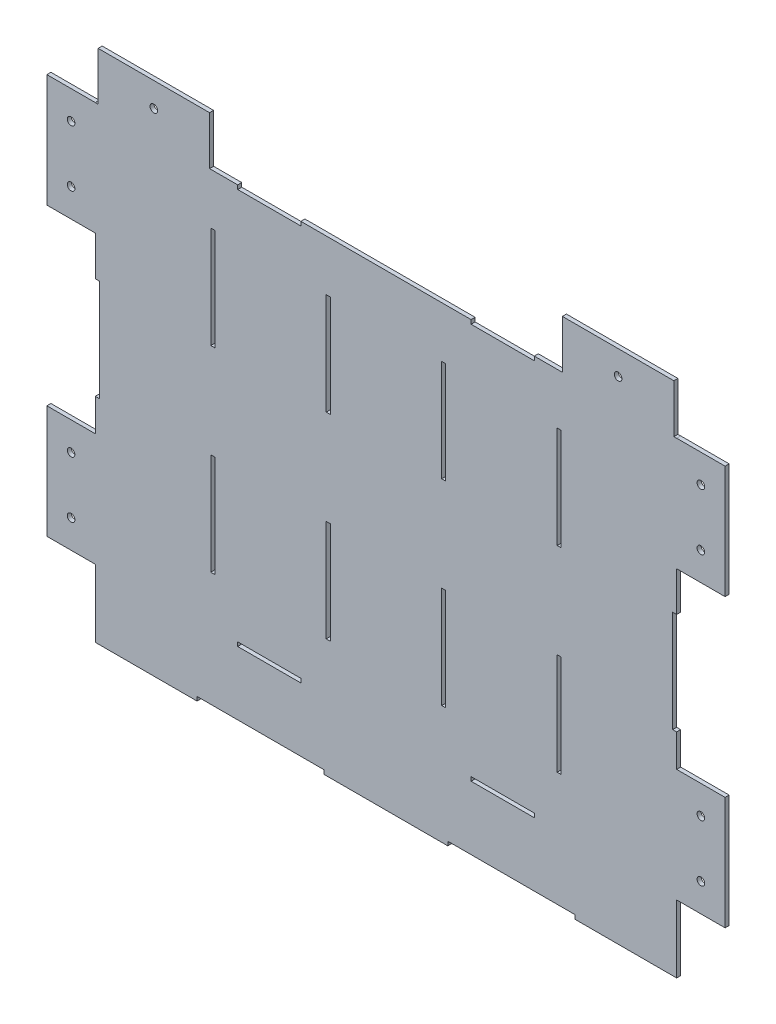
SolidWorks part; units mm, degrees
material "Custom Plastic"
ref_plane "X-Y Datum" through (0, 0, 0) normal (0, 0, 1) x (1, 0, 0)
ref_plane "X-Z Datum" through (0, 0, 0) normal (0, 1, 0) x (1, 0, 0)
ref_plane "Y-Z Datum" through (0, 0, 0) normal (1, 0, 0) x (0, 0, -1)
sketch "Sketch1" plane through (0, 0, 0) normal (0, 0, 1) x (1, 0, 0)
  line L0 (-228.6115, 0) -> (228.6115, 0) construction
  line L1 (-228.6115, -157.216) -> (228.6115, -157.216)
  line L2 (-228.6115, -157.216) -> (-228.6115, 157.216)
  line L3 (-228.6115, 157.216) -> (228.6115, 157.216)
  line L4 (228.6115, -157.216) -> (228.6115, 157.216)
  line L5 (-228.6115, -157.216) -> (228.6115, 157.216) construction
  line L6 (-228.6115, 157.216) -> (228.6115, -157.216) construction
  line L8 (-228.6115, 0) -> (-134.6215, 0) construction
  line L9 (-225.4325, -154.041) -> (-225.4325, 154.041)
  line L10 (-224.4165, -153.025) -> (-138.8165, -153.025) construction
  line L15 (-224.4165, -153.025) -> (-224.4165, 153.025) construction
  line L16 (-224.4165, 153.025) -> (-138.8165, 153.025) construction
  line L17 (-138.8165, -153.025) -> (-138.8165, 153.025) construction
  line L18 (-224.4165, -153.025) -> (-138.8165, 153.025) construction
  line L19 (-224.4165, 153.025) -> (-138.8165, -153.025) construction
  line L20 (-225.4325, 154.041) -> (-137.8005, 154.041)
  line L21 (-137.8005, -154.041) -> (-137.8005, 154.041)
  line L22 (-225.4325, -154.041) -> (-137.8005, -154.041)
  line L26 (-134.6255, 154.041) -> (-46.9935, 154.041)
  line L27 (-133.6095, -153.025) -> (-48.0095, -153.025) construction
  line L28 (-133.6095, -153.025) -> (-133.6095, 153.025) construction
  line L29 (-133.6095, 153.025) -> (-48.0095, 153.025) construction
  line L30 (-48.0095, -153.025) -> (-48.0095, 153.025) construction
  line L31 (-133.6095, -153.025) -> (-48.0095, 153.025) construction
  line L32 (-133.6095, 153.025) -> (-48.0095, -153.025) construction
  line L33 (-46.9935, -154.041) -> (-46.9935, 154.041)
  line L34 (-134.6255, -154.041) -> (-46.9935, -154.041)
  line L35 (-134.6255, -154.041) -> (-134.6255, 154.041)
  line L36 (42.7975, -153.025) -> (42.7975, 153.025) construction
  line L37 (43.8135, -154.041) -> (43.8135, 154.041)
  line L38 (-42.8025, -153.025) -> (42.7975, 153.025) construction
  line L39 (-42.8025, 153.025) -> (42.7975, -153.025) construction
  line L40 (-42.8025, -153.025) -> (-42.8025, 153.025) construction
  line L41 (-43.8185, -154.041) -> (-43.8185, 154.041)
  line L42 (-42.8025, 153.025) -> (42.7975, 153.025) construction
  line L43 (-43.8185, 154.041) -> (43.8135, 154.041)
  line L44 (-42.8025, -153.025) -> (42.7975, -153.025) construction
  line L45 (-43.8185, -154.041) -> (43.8135, -154.041)
  line L46 (133.6045, -153.025) -> (133.6045, 153.025) construction
  line L47 (134.6205, -154.041) -> (134.6205, 154.041)
  line L48 (48.0045, -153.025) -> (133.6045, 153.025) construction
  line L49 (48.0045, 153.025) -> (133.6045, -153.025) construction
  line L50 (48.0045, -153.025) -> (48.0045, 153.025) construction
  line L51 (46.9885, -154.041) -> (46.9885, 154.041)
  line L52 (48.0045, 153.025) -> (133.6045, 153.025) construction
  line L53 (46.9885, 154.041) -> (134.6205, 154.041)
  line L54 (48.0045, -153.025) -> (133.6045, -153.025) construction
  line L55 (46.9885, -154.041) -> (134.6205, -154.041)
  line L56 (224.4115, -153.025) -> (224.4115, 153.025) construction
  line L57 (225.4275, -154.041) -> (225.4275, 154.041)
  line L58 (138.8115, -153.025) -> (224.4115, 153.025) construction
  line L59 (138.8115, 153.025) -> (224.4115, -153.025) construction
  line L60 (138.8115, -153.025) -> (138.8115, 153.025) construction
  line L61 (137.7955, -154.041) -> (137.7955, 154.041)
  line L62 (138.8115, 153.025) -> (224.4115, 153.025) construction
  line L63 (137.7955, 154.041) -> (225.4275, 154.041)
  line L64 (138.8115, -153.025) -> (224.4115, -153.025) construction
  line L65 (137.7955, -154.041) -> (225.4275, -154.041)
  line L67 (-228.6115, -157.216) -> (225.4365, -157.216)
  line L71 (-228.6115, -157.216) -> (228.6115, -157.216)
  line L74 (-225.4365, -157.216) -> (225.4365, -157.216)
  line L75 (-225.4365, -157.216) -> (-225.4365, -208.106)
  line L76 (-225.4365, -208.106) -> (225.4365, -208.106)
  line L77 (225.4365, -157.216) -> (225.4365, -208.106)
  line L79 (-228.6115, -157.216) -> (228.6115, -157.216)
  line L80 (-228.6115, -157.216) -> (-228.6115, -210.392)
  line L81 (-228.6115, -210.392) -> (228.6115, -210.392)
  line L82 (228.6115, -157.216) -> (228.6115, -210.392)
  point P0 (0, 0)
  point P10 (-181.6165, 0)
  point P22 (-90.8095, 0)
  dimension "D1" = 314.432
  dimension "D2" = 457.223
  dimension "D4" = 1.016
  dimension "D5" = 3.179
  dimension "D6" = 3.175
  dimension "D7" = 1.016
  dimension "D8" = 90.807
  dimension "D9" = 3.175
  dimension "D11" = 3.175
  dimension "D12" = 50.89
  dimension "D13" = 2.286
  dimension "D14" = 3.175
  dimension "D15" = 3.175
  dimension "D10" = 4
extrude "Boss-Extrude2" add sketch "Sketch1" along normal blind 3.175 contours L61 L65 L57 L63 | L51 L55 L47 L53 | L41 L45 L37 L43 | L35 L34 L33 L26 | L9 L22 L21 L20 | L1 L71 L4 L3 L2 L65 L61 L63 L57 L55 L51 L53 L47 L45 L41 L43 L37 L22 L9 L20 L21 L34 L35 L26 L33 | L77 L71 L75 L76 | L82 L1 L77 L76 L75 L80 L81 region at (-228.0566, 0, 0) region at (-227.024, -161.819, 0) region at (0, -182.661, 0) region at (-181.6165, 0, 0) region at (-90.8095, 0, 0) region at (-0.0025, 0, 0) region at (90.8045, 0, 0) region at (181.6115, 0, 0)
sketch "Sketch4" plane through (0, 0, 3.175) normal (0, 0, 1) x (1, 0, 0)
  line L0 (-136.213, 117.216) -> (-136.213, 157.216) construction
  line L1 (-228.6115, 157.216) -> (228.6115, 157.216) construction
  line L2 (-228.6115, 157.216) -> (228.6115, 157.216) construction
  line L5 (-134.6255, -154.041) -> (-134.6255, 154.041) construction
  line L6 (-137.8005, 37.216) -> (-134.6255, 37.216)
  line L7 (-137.8005, 37.216) -> (-137.8005, 117.216)
  line L8 (-137.8005, 117.216) -> (-134.6255, 117.216)
  line L9 (-134.6255, 37.216) -> (-134.6255, 117.216)
  line L10 (-137.8005, 37.216) -> (-134.6255, 117.216) construction
  line L11 (-137.8005, 117.216) -> (-134.6255, 37.216) construction
  line L13 (-45.406, 153.025) -> (-45.406, -157.216) construction
  line L14 (-228.6115, -157.216) -> (228.6115, -157.216) construction
  dimension "D1" = 40
  dimension "D2" = 3.175
  dimension "D3" = 80
  dimension "D4" = 90.807
extrude "Cut-Extrude1" cut sketch "Sketch4" against normal blind 3.175 contours L6 L9 L8 L7 region at (-136.213, 77.216, 3.175)
mirror "Mirror1" about plane through (0, 0, 0) normal (0, 1, 0) of "Cut-Extrude1"
pattern_linear "LPattern1" count 4 spacing 90.807 along (1, 0, 0) of "Mirror1"
sketch "Sketch5" plane through (0, 0, 3.175) normal (0, 0, 1) x (1, 0, 0)
  line L0 (-225.4365, -157.216) -> (-228.6115, -157.216)
  line L1 (-225.4325, -154.041) -> (-228.6115, -154.041)
  line L2 (-228.6115, -157.216) -> (-228.6115, 157.216) construction
  line L3 (-228.6115, -154.041) -> (-228.6115, -157.216)
  line L4 (-228.6115, -155.6285) -> (-194.996, -155.6285)
  line L5 (-194.996, -155.6285) -> (-91.7821, -155.6285) construction
  line L6 (-225.4325, -154.041) -> (-137.8005, -154.041) construction
  line L7 (-116.6115, -157.216) -> (-66.9527, -157.216)
  line L8 (-116.6115, -157.216) -> (-116.6115, -154.041)
  line L9 (-116.6115, -154.041) -> (-66.9527, -154.041)
  line L10 (-66.9527, -157.216) -> (-66.9527, -154.041)
  line L11 (-116.6115, -157.216) -> (-66.9527, -154.041) construction
  line L12 (-116.6115, -154.041) -> (-66.9527, -157.216) construction
  dimension "D1" = 112
  dimension "D2" = 49.6588
extrude "Cut-Extrude2" cut sketch "Sketch5" against normal blind 3.175 contours L7 L10 L9 L8 region at (-91.7821, -155.6285, 3.175)
mirror "Mirror2" about plane through (0, 0, 0) normal (1, 0, 0) of "Cut-Extrude2"
mirror "Mirror3" about plane through (0, 0, 0) normal (0, 1, 0) of "Mirror2"
sketch "Sketch6" plane through (0, 0, 3.175) normal (0, 0, 1) x (1, 0, 0)
  line L0 (-228.6115, -210.392) -> (-228.6115, 157.216) construction
  line L3 (-228.6115, 157.216) -> (-116.6115, 157.216) construction
  line L5 (-225.4365, 157.216) -> (-228.6115, 157.216)
  line L6 (-227.024, 157.216) -> (-227.024, 37.216) construction
  line L7 (-227.024, 37.216) -> (-227.024, -42.784) construction
  line L9 (-225.4365, -42.784) -> (-228.6115, -42.784)
  line L10 (-225.4365, -42.784) -> (-225.4365, 37.216)
  line L11 (-225.4365, 37.216) -> (-228.6115, 37.216)
  line L12 (-228.6115, -42.784) -> (-228.6115, 37.216)
  line L13 (-225.4365, -42.784) -> (-228.6115, 37.216) construction
  line L14 (-225.4365, 37.216) -> (-228.6115, -42.784) construction
  point P11 (-227.024, -2.784)
  dimension "D1" = 3.175
  dimension "D2" = 120
  dimension "D3" = 80
extrude "Cut-Extrude3" cut sketch "Sketch6" against normal through all contours L12 L9 L10 L11 region at (-227.024, -2.784, 3.175)
mirror "Mirror5" about plane through (0, 0, 0) normal (1, 0, 0) of "Cut-Extrude3"
sketch "Sketch7" plane through (0, 0, 3.175) normal (0, 0, 1) x (1, 0, 0)
  line L1 (-228.6115, -210.392) -> (-228.6115, -42.784) construction
  line L5 (-148.6115, -210.392) -> (-48.6115, -210.392)
  line L6 (-148.6115, -210.392) -> (-148.6115, -207.217)
  line L7 (-148.6115, -207.217) -> (-48.6115, -207.217)
  line L8 (-48.6115, -210.392) -> (-48.6115, -207.217)
  line L9 (-148.6115, -210.392) -> (-48.6115, -207.217) construction
  line L10 (-148.6115, -207.217) -> (-48.6115, -210.392) construction
  point P7 (-98.6115, -208.8045)
  dimension "D1" = 80
  dimension "D2" = 100
  dimension "D3" = 3.175
extrude "Cut-Extrude4" cut sketch "Sketch7" against normal blind 3.175 contours L5 L8 L7 L6 region at (-98.6115, -208.8045, 3.175)
mirror "Mirror6" about plane through (0, 0, 0) normal (1, 0, 0) of "Cut-Extrude4"
sketch "Sketch9" plane through (0, 0, 3.175) normal (0, 0, 1) x (1, 0, 0)
  line L0 (-136.213, 77.216) -> (-136.213, -68.834)
  line L1 (-137.8005, 37.216) -> (-134.6255, 117.216) construction
  dimension "D1" = 146.05
sketch "Sketch10" plane through (0, 0, 0) normal (0, 0, -1) x (-1, 0, 0)
  line L10 (-228.6115, -210.392) -> (-228.6115, -42.784) construction
  line L11 (-228.6115, 157.273) -> (-266.7115, 157.273)
  line L12 (-228.6115, 157.273) -> (-228.6115, 68.373)
  line L13 (-228.6115, 68.373) -> (-266.7115, 68.373)
  line L14 (-266.7115, 157.273) -> (-266.7115, 68.373)
  line L15 (-228.6115, -157.216) -> (-266.7115, -157.216)
  line L16 (-228.6115, -157.216) -> (-228.6115, -68.316)
  line L17 (-228.6115, -68.316) -> (-266.7115, -68.316)
  line L18 (-266.7115, -157.216) -> (-266.7115, -68.316)
  line L19 (-137.8065, -157.216) -> (-266.7115, -157.216) construction
  line L20 (-247.6615, 157.273) -> (-247.6615, 68.373) construction
  line L21 (-266.7115, 112.823) -> (-228.6115, 112.823)
  line L22 (-247.6615, 157.273) -> (-247.6615, 112.823) construction
  line L23 (-247.6615, -68.316) -> (-247.6615, -157.216) construction
  line L24 (-266.7115, -112.766) -> (-228.6115, -112.766)
  line L25 (-247.6615, -68.316) -> (-247.6615, -112.766) construction
  line L26 (-250.6615, 135.048) -> (-250.6615, 157.273) construction
  circle A0 centre (-247.6615, 135.048) radius 3
  circle A1 centre (-247.6615, 90.598) radius 3
  circle A2 centre (-247.6615, -90.541) radius 3
  circle A3 centre (-247.6615, -134.991) radius 3
  dimension "D2" = 16.05
  dimension "D3" = 6
  dimension "D1" = 88.9
  dimension "D4" = 19.05
extrude "Boss-Extrude3" add sketch "Sketch10" against normal blind 3.175 contours L18 L24 L16 L17 A2 | L24 L18 L15 L16 A3 | L14 L21 L12 L11 A0 | L21 L14 L13 L12 A1 region at (229.1969, 135.048, 0) region at (229.1969, 90.598, 0) region at (247.6615, -156.6306, 0) region at (247.6615, -112.1806, 0)
mirror "Mirror7" about plane through (0, 0, 0) normal (1, 0, 0) of "Boss-Extrude3"
sketch "Sketch12" plane through (0, 0, 0) normal (0, 0, -1) x (-1, 0, 0)
  line L0 (-226.389, 176.266) -> (-138.759, 176.266) construction
  line L5 (-226.389, 157.216) -> (-138.759, 157.216)
  line L10 (-226.389, 157.216) -> (-226.389, 195.316)
  line L11 (-226.389, 195.316) -> (-138.759, 195.316)
  line L12 (-138.759, 157.216) -> (-138.759, 195.316)
  line L13 (-182.574, 179.266) -> (-226.389, 179.266) construction
  circle A1 centre (-182.574, 176.266) radius 3
  dimension "D2" = 19.05
  dimension "D1" = 87.63
  dimension "D3" = 16.05
extrude "Boss-Extrude4" add sketch "Sketch12" against normal blind 3.175 contours L5 L12 L11 L10 A1 region at (225.4335, 176.266, 0)
mirror "Mirror8" about plane through (0, 0, 0) normal (1, 0, 0) of "Boss-Extrude4"
